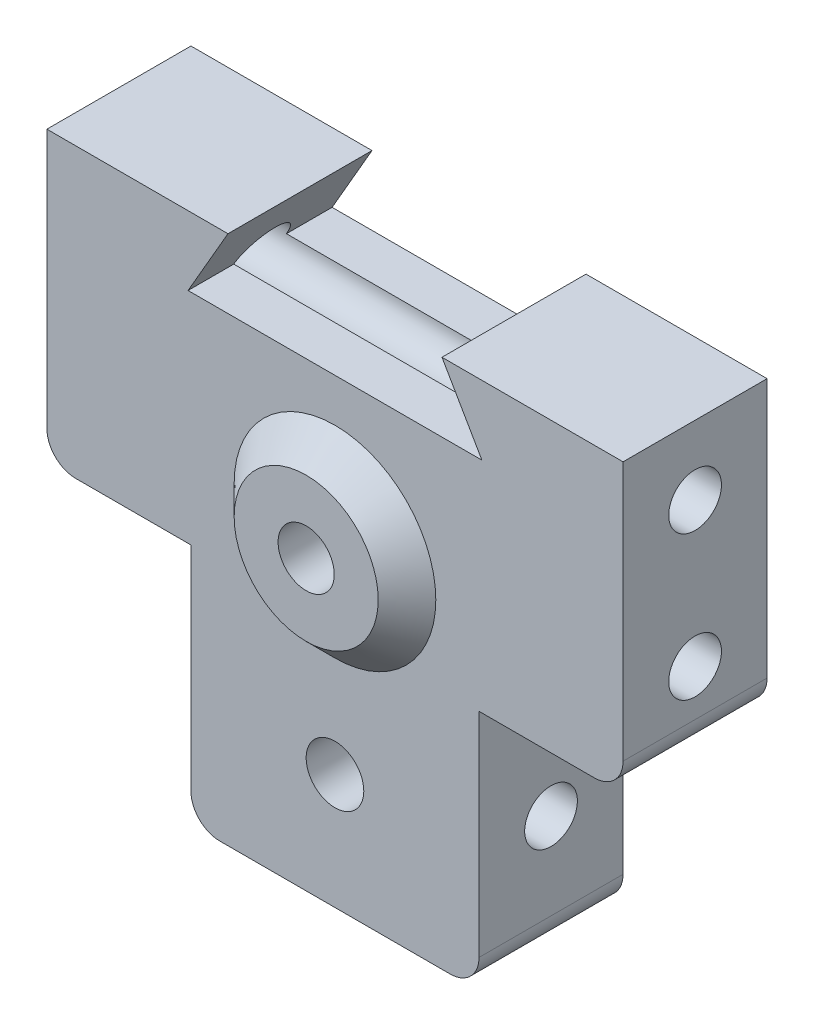
SolidWorks part; units mm, degrees
ref_plane "Front Plane" through (0, 0, 0) normal (0, 0, 1) x (1, 0, 0)
ref_plane "Top Plane" through (0, 0, 0) normal (0, 1, 0) x (1, 0, 0)
ref_plane "Right Plane" through (0, 0, 0) normal (1, 0, 0) x (0, 0, -1)
sketch "Sketch1" plane through (0, 0, 0) normal (0, 1, 0) x (1, 0, 0)
  line L1 (-10, -2.5) -> (10, -2.5)
  line L2 (-10, -2.5) -> (-10, 2.5)
  line L3 (-10, 2.5) -> (10, 2.5)
  line L4 (10, -2.5) -> (10, 2.5)
  line L5 (-10, -2.5) -> (10, 2.5) construction
  line L6 (-10, 2.5) -> (10, -2.5) construction
  point P0 (0, 0)
  dimension "D1" = 5
  dimension "D2" = 20
extrude "Boss-Extrude1" add sketch "Sketch1" along normal blind 10
sketch "Sketch2" plane through (0, 0, 2.5) normal (0, 0, 1) x (1, 0, 0)
  line L0 (0, 0) -> (0, 10) construction
  line L1 (-10, 10) -> (10, 10) construction
  line L2 (3.7144, 10) -> (-3.7144, 10)
  line L3 (-3.7144, 10) -> (-5.1, 7.6)
  line L4 (-5.1, 7.6) -> (5.1, 7.6)
  line L5 (3.7144, 10) -> (5.1, 7.6)
  point P9 (0, 7.6)
  dimension "D1" = 60
  dimension "D2" = 10.2
  dimension "D3" = 2.4
extrude "Cut-Extrude1" cut sketch "Sketch2" against normal through all
sketch "Sketch8" plane through (10, 0, 0) normal (1, 0, 0) x (0, 0, -1)
  line L2 (2.5, 7.6) -> (-2.5, 7.6) construction
  line L3 (2.5, 7.6) -> (-2.5, 7.6) construction
  circle A0 centre (0, 7.6) radius 0.915
  dimension "D1" = 1.83
extrude "Cut-Extrude6" cut sketch "Sketch8" against normal through all
sketch "Sketch7" plane through (10, 0, 0) normal (1, 0, 0) x (0, 0, -1)
  line L0 (0, 7.6) -> (0, 2.6) construction
  line L3 (2.5, 7.6) -> (0.915, 7.6) construction
  circle A0 centre (0, 2.6) radius 0.915
  dimension "D1" = 1.83
  dimension "D2" = 5
extrude "Cut-Extrude5" cut sketch "Sketch7" against normal through all
sketch "Sketch10" plane through (0, 0, 2.5) normal (0, 0, 1) x (1, 0, 0)
  line L0 (10, 1.685) -> (10, 3.515) construction
  line L1 (10, 1.685) -> (10, 3.515) construction
  line L2 (10, 2.6) -> (-10, 2.6) construction
  line L3 (-10, 10) -> (-10, 0) construction
  circle A0 centre (0, 2.6) radius 2.5
  dimension "D1" = 5
extrude "Boss-Extrude4" add sketch "Sketch10" along normal blind 1
sketch "Sketch5" plane through (0, 0, -2.5) normal (0, 0, -1) x (-1, 0, 0)
  line L0 (-10, 0) -> (10, 0) construction
  line L1 (-5, -8.4) -> (5, -8.4)
  line L2 (-5, -8.4) -> (-5, 0)
  line L3 (-5, 0) -> (5, 0)
  line L4 (5, -8.4) -> (5, 0)
  line L5 (-5, -8.4) -> (5, 0) construction
  line L6 (-5, 0) -> (5, -8.4) construction
  line L7 (0, 0) -> (0, -4.2) construction
  line L9 (5.1, 7.6) -> (-5.1, 7.6) construction
  point P0 (0, -4.2)
  dimension "D1" = 16
  dimension "D2" = 10
extrude "Boss-Extrude3" add sketch "Sketch5" against normal up to surface (5 mm away) up to face at (-2.5, 2.6, 2.5)
sketch "Sketch6" plane through (0, 0, 2.5) normal (0, 0, 1) x (1, 0, 0)
  line L0 (0, -8.4) -> (0, -4.4) construction
  line L1 (-5, -8.4) -> (5, -8.4) construction
  line L3 (-5.1, 7.6) -> (5.1, 7.6) construction
  circle A0 centre (0, -4.4) radius 1
  dimension "D1" = 2
  dimension "D2" = 12
extrude "Cut-Extrude4" cut sketch "Sketch6" against normal through all
sketch "Sketch9" plane through (5, 0, 0) normal (1, 0, 0) x (0, 0, -1)
  line L0 (-2.5, -3.4) -> (-2.5, -5.4) construction
  line L1 (-2.5, -3.4) -> (-2.5, -5.4) construction
  line L2 (-2.5, -4.4) -> (2.5, -4.4) construction
  line L3 (2.5, 0) -> (2.5, -8.4) construction
  circle A0 centre (0, -4.4) radius 0.915
  dimension "D1" = 1.83
extrude "Cut-Extrude7" cut sketch "Sketch9" against normal up to surface (10 mm away) up to face at (-5, -4.2, 0)
sketch "Sketch11" plane through (0, 0, 3.5) normal (0, 0, 1) x (1, 0, 0)
  circle A0 centre (0, 2.6) radius 0.975
  dimension "D1" = 1.95
extrude "Cut-Extrude8" cut sketch "Sketch11" against normal through all
chamfer "Chamfer1" distance 1 angle 45 1 edges at (-2.5, 2.6, 2.5)
fillet "Fillet1" radius 1 4 edges at (-5, -8.4, 0) (-10, 0, 0) (5, -8.4, 0) (10, 0, 0)
